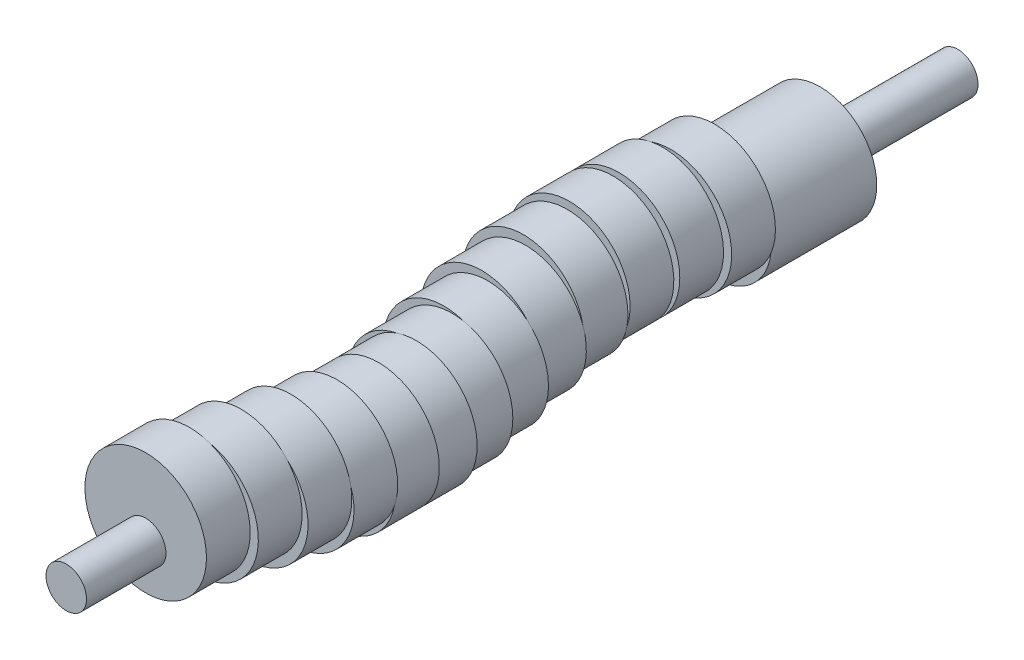
SolidWorks part; units mm, degrees
ref_plane "Front Plane" through (0, 0, 0) normal (0, 0, 1) x (1, 0, 0)
ref_plane "Top Plane" through (0, 0, 0) normal (0, 1, 0) x (1, 0, 0)
ref_plane "Right Plane" through (0, 0, 0) normal (1, 0, 0) x (0, 0, -1)
sketch "Sketch1" plane through (0, 0, 0) normal (0, 0, 1) x (1, 0, 0)
  line L0 (0, 0) -> (0, 2) construction
  circle A0 centre (0, 0) radius 2.5
  circle A1 centre (0, 2) radius 7.5
  dimension "D1" = 5
  dimension "D3" = 15
  dimension "D2" = 2
extrude "Boss-Extrude1" add sketch "Sketch1" along normal blind 5.4
ref_plane "Plane1" through (0, 0, 0) normal (0, 0, -1) x (-1, 0, 0)
sketch "Sketch2" plane through (0, 0, 0) normal (0, 0, -1) x (-1, 0, 0)
  line L0 (0, 0) -> (0, 2.5) construction
  line L1 (0, 0) -> (-1, 1.7321) construction
  circle A0 centre (0, 0) radius 2.5
  circle A1 centre (-1, 1.7321) radius 7.5
  dimension "D3" = 5
  dimension "D4" = 15
  dimension "D1" = 30
  dimension "D2" = 2
extrude "Boss-Extrude2" add sketch "Sketch2" along normal blind 5.4
ref_plane "Plane2" through (0, 0, -5.4) normal (0, 0, -1) x (-1, 0, 0)
sketch "Sketch3" plane through (0, 0, -5.4) normal (0, 0, -1) x (-1, 0, 0)
  line L0 (0, 0) -> (0, 2.5) construction
  line L1 (0, 0) -> (-1.7321, 1) construction
  circle A0 centre (0, 0) radius 2.5 construction
  circle A1 centre (-1.7321, 1) radius 7.5
  circle A2 centre (0, 0) radius 2.5
  dimension "D3" = 15
  dimension "D4" = 5
  dimension "D1" = 60
  dimension "D2" = 2
extrude "Boss-Extrude3" add sketch "Sketch3" along normal blind 5.4
ref_plane "Plane3" through (0, 0, -10.8) normal (0, 0, -1) x (-1, 0, 0)
sketch "Sketch4" plane through (0, 0, -10.8) normal (0, 0, -1) x (-1, 0, 0)
  line L0 (0, 0) -> (0, 2.5) construction
  line L1 (0, 0) -> (-2, 0) construction
  circle A0 centre (0, 0) radius 2.5
  circle A2 centre (-2, 0) radius 7.5
  dimension "D3" = 5
  dimension "D4" = 15
  dimension "D1" = 90
  dimension "D2" = 2
extrude "Boss-Extrude4" add sketch "Sketch4" along normal blind 5.4
ref_plane "Plane4" through (0, 0, -16.2) normal (0, 0, -1) x (-1, 0, 0)
sketch "Sketch5" plane through (0, 0, -16.2) normal (0, 0, -1) x (-1, 0, 0)
  line L0 (0, 0) -> (-2.5, 0) construction
  line L1 (0, 0) -> (-1.7321, -1) construction
  circle A0 centre (0, 0) radius 2.5
  circle A1 centre (-1.7321, -1) radius 7.5
  dimension "D2" = 5
  dimension "D4" = 15
  dimension "D1" = 30
  dimension "D3" = 2
extrude "Boss-Extrude5" add sketch "Sketch5" along normal blind 5.4
ref_plane "Plane5" through (0, 0, -21.6) normal (0, 0, -1) x (-1, 0, 0)
sketch "Sketch6" plane through (0, 0, -21.6) normal (0, 0, -1) x (-1, 0, 0)
  line L0 (0, 0) -> (-2.5, 0) construction
  line L1 (0, 0) -> (-1, -1.7321) construction
  circle A0 centre (0, 0) radius 2.5
  circle A1 centre (-1, -1.7321) radius 7.5
  dimension "D2" = 5
  dimension "D4" = 15
  dimension "D1" = 60
  dimension "D3" = 2
extrude "Boss-Extrude6" add sketch "Sketch6" along normal blind 5.4
ref_plane "Plane6" through (0, 0, -27) normal (0, 0, -1) x (-1, 0, 0)
sketch "Sketch7" plane through (0, 0, -27) normal (0, 0, -1) x (-1, 0, 0)
  line L0 (0, 0) -> (0, -2) construction
  circle A0 centre (0, 0) radius 2.5
  circle A1 centre (0, -2) radius 7.5
  dimension "D2" = 5
  dimension "D3" = 15
  dimension "D1" = 2
extrude "Boss-Extrude7" add sketch "Sketch7" along normal blind 5.4
ref_plane "Plane7" through (0, 0, -32.4) normal (0, 0, -1) x (-1, 0, 0)
sketch "Sketch8" plane through (0, 0, -32.4) normal (0, 0, -1) x (-1, 0, 0)
  line L0 (0, -2.5) -> (0, 0) construction
  line L1 (0, 0) -> (1, -1.7321) construction
  circle A0 centre (0, 0) radius 2.5
  circle A1 centre (1, -1.7321) radius 7.5
  dimension "D2" = 5
  dimension "D4" = 15
  dimension "D1" = 30
  dimension "D3" = 2
extrude "Boss-Extrude9" add sketch "Sketch8" along normal blind 5.4
ref_plane "Plane8" through (0, 0, -37.8) normal (0, 0, -1) x (-1, 0, 0)
sketch "Sketch9" plane through (0, 0, -37.8) normal (0, 0, -1) x (-1, 0, 0)
  line L0 (0, -2.5) -> (0, 0) construction
  line L1 (0, 0) -> (1.7321, -1) construction
  circle A0 centre (0, 0) radius 2.5
  circle A1 centre (1.7321, -1) radius 7.5
  dimension "D1" = 5
  dimension "D4" = 15
  dimension "D2" = 60
  dimension "D3" = 2
extrude "Boss-Extrude10" add sketch "Sketch9" along normal blind 5.4
ref_plane "Plane9" through (0, 0, -43.2) normal (0, 0, -1) x (-1, 0, 0)
sketch "Sketch10" plane through (0, 0, -43.2) normal (0, 0, -1) x (-1, 0, 0)
  line L0 (0, 0) -> (2, 0) construction
  circle A0 centre (0, 0) radius 2.5
  circle A1 centre (2, 0) radius 7.5
  dimension "D1" = 5
  dimension "D3" = 15
  dimension "D2" = 2
extrude "Boss-Extrude11" add sketch "Sketch10" along normal blind 5.4
ref_plane "Plane10" through (0, 0, -48.6) normal (0, 0, -1) x (-1, 0, 0)
sketch "Sketch11" plane through (0, 0, -48.6) normal (0, 0, -1) x (-1, 0, 0)
  line L0 (2.5, 0) -> (0, 0) construction
  line L1 (0, 0) -> (1.7321, 1) construction
  circle A0 centre (0, 0) radius 2.5
  circle A1 centre (1.7321, 1) radius 7.5
  dimension "D3" = 5
  dimension "D4" = 15
  dimension "D1" = 30
  dimension "D2" = 2
extrude "Boss-Extrude12" add sketch "Sketch11" along normal blind 5.4
ref_plane "Plane11" through (0, 0, -54) normal (0, 0, -1) x (-1, 0, 0)
sketch "Sketch12" plane through (0, 0, -54) normal (0, 0, -1) x (-1, 0, 0)
  line L0 (2.5, 0) -> (0, 0) construction
  line L1 (0, 0) -> (1, 1.7321) construction
  circle A0 centre (0, 0) radius 2.5
  circle A1 centre (1, 1.7321) radius 7.5
  dimension "D2" = 5
  dimension "D4" = 15
  dimension "D1" = 60
  dimension "D3" = 2
extrude "Boss-Extrude13" add sketch "Sketch12" along normal blind 5.4
ref_plane "Plane12" through (0, 0, -59.4) normal (0, 0, -1) x (-1, 0, 0)
sketch "Sketch13" plane through (0, 0, -59.4) normal (0, 0, -1) x (-1, 0, 0)
  line L0 (0, 0) -> (0, 2) construction
  circle A0 centre (0, 0) radius 2.5
  circle A1 centre (0, 2) radius 7.5
  dimension "D2" = 5
  dimension "D3" = 15
  dimension "D1" = 2
extrude "Boss-Extrude14" add sketch "Sketch13" along normal blind 5.4
sketch "Sketch14" plane through (0, 0, -64.8) normal (0, 0, -1) x (-1, 0, 0)
  circle A0 centre (0, 0) radius 2.5
  dimension "D1" = 5
extrude "Boss-Extrude15" add sketch "Sketch14" against normal blind 80
extrude "Boss-Extrude16" add sketch "Sketch14<2>" along normal blind 30
sketch "Sketch14<2>" plane through (0, 0, -64.8) normal (0, 0, -1) x (-1, 0, 0) same geometry as "Sketch14"
sketch "Sketch15" plane through (0, 0, -64.8) normal (0, 0, -1) x (-1, 0, 0)
  circle A0 centre (0, 0) radius 7
  dimension "D1" = 14
extrude "Boss-Extrude17" add sketch "Sketch15" along normal blind 13
